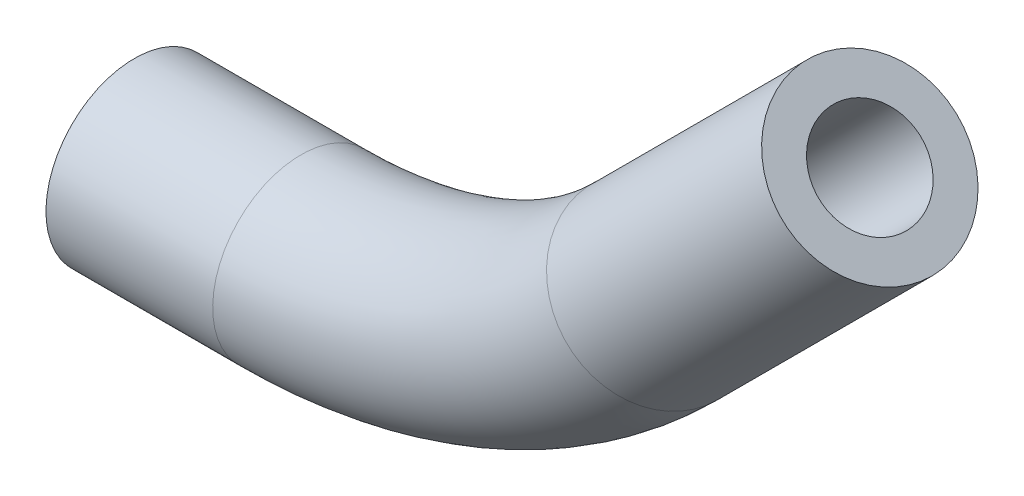
SolidWorks part; units mm, degrees
material "Rubber"
ref_plane "X-Y Datum" through (0, 0, 0) normal (0, 0, 1) x (1, 0, 0)
ref_plane "X-Z Datum" through (0, 0, 0) normal (0, 1, 0) x (1, 0, 0)
ref_plane "Y-Z Datum" through (0, 0, 0) normal (1, 0, 0) x (0, 0, -1)
sketch "Sketch1" plane through (0, 0, 0) normal (0, 0, 1) x (1, 0, 0)
  line L0 (0, 0) -> (25.4, 0)
  line L1 (55.1739, 0) -> (-55.1739, 0) construction
  line L2 (79.2815, 22.3185) -> (112.0485, 55.0854)
  arc A0 (25.4, 0) -> (79.2815, 22.3185) centre (25.4, 76.2) ccw
  dimension "D3" = 76.2
  dimension "D1" = 25.4
  dimension "D2" = 135
sweep "Sweep1" add path "Sketch1" circular profile diameter 26.924 parameters "D3"=26.924
sweep "Cut-Sweep1" cut path "Sketch1<2>" circular profile diameter 15.748 parameters "D3"=15.748
sketch "Sketch1<2>" plane through (0, 0, 0) normal (0, 0, 1) x (1, 0, 0) same geometry as "Sketch1"
